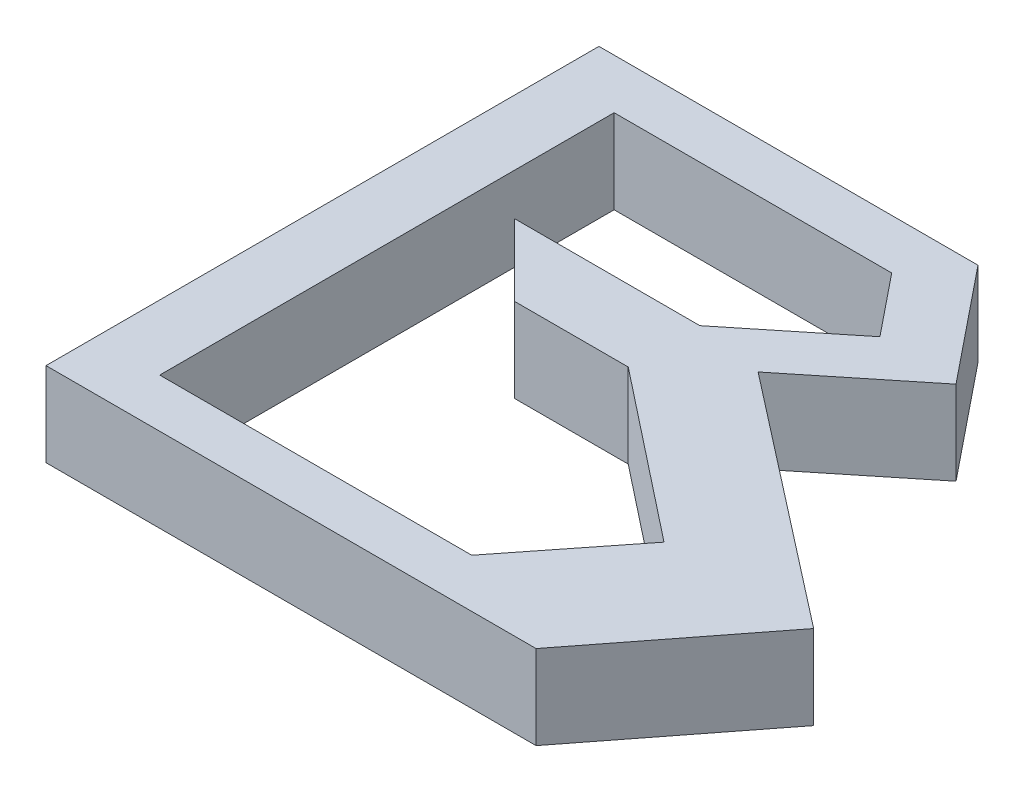
SolidWorks part; units mm, degrees
ref_plane "Front Plane" through (0, 0, 0) normal (0, 0, 1) x (1, 0, 0)
ref_plane "Top Plane" through (0, 0, 0) normal (0, 1, 0) x (1, 0, 0)
ref_plane "Right Plane" through (0, 0, 0) normal (1, 0, 0) x (0, 0, -1)
sketch "Sketch1" plane through (0, 0, 0) normal (0, 1, 0) x (1, 0, 0)
  line L0 (-31.5914, 41.6491) -> (-31.5914, -24.1126)
  line L1 (-31.5914, -24.1126) -> (26.6915, -24.1126)
  line L2 (26.6915, -24.1126) -> (41.1333, -5.5446)
  line L3 (41.1333, -5.5446) -> (11.4066, 17.5761)
  line L4 (11.4066, 17.5761) -> (24.4311, 28.0888)
  line L5 (24.4311, 28.0888) -> (13.4859, 41.6491)
  line L6 (13.4859, 41.6491) -> (-31.5914, 41.6491)
  line L7 (-23.8547, 35.7176) -> (9.1551, 35.7176)
  line L8 (9.1551, 35.7176) -> (15.0229, 28.4478)
  line L9 (15.0229, 28.4478) -> (3.1728, 18.8831)
  line L10 (3.1728, 18.8831) -> (-18.8831, 18.8831)
  line L11 (-18.8831, 18.8831) -> (-10.3652, 10.3652)
  line L12 (-10.3652, 10.3652) -> (3.1728, 10.3652)
  line L13 (3.1728, 10.3652) -> (23.3389, -5.5446)
  line L14 (23.3389, -5.5446) -> (13.2559, -18.3252)
  line L15 (13.2559, -18.3252) -> (-23.8547, -18.3252)
  line L16 (-23.8547, -18.3252) -> (-23.8547, 35.7176)
  point P9 (13.4859, 41.6491)
  point P18 (9.1551, 35.7176)
extrude "Boss-Extrude1" add sketch "Sketch1" along normal blind 10
